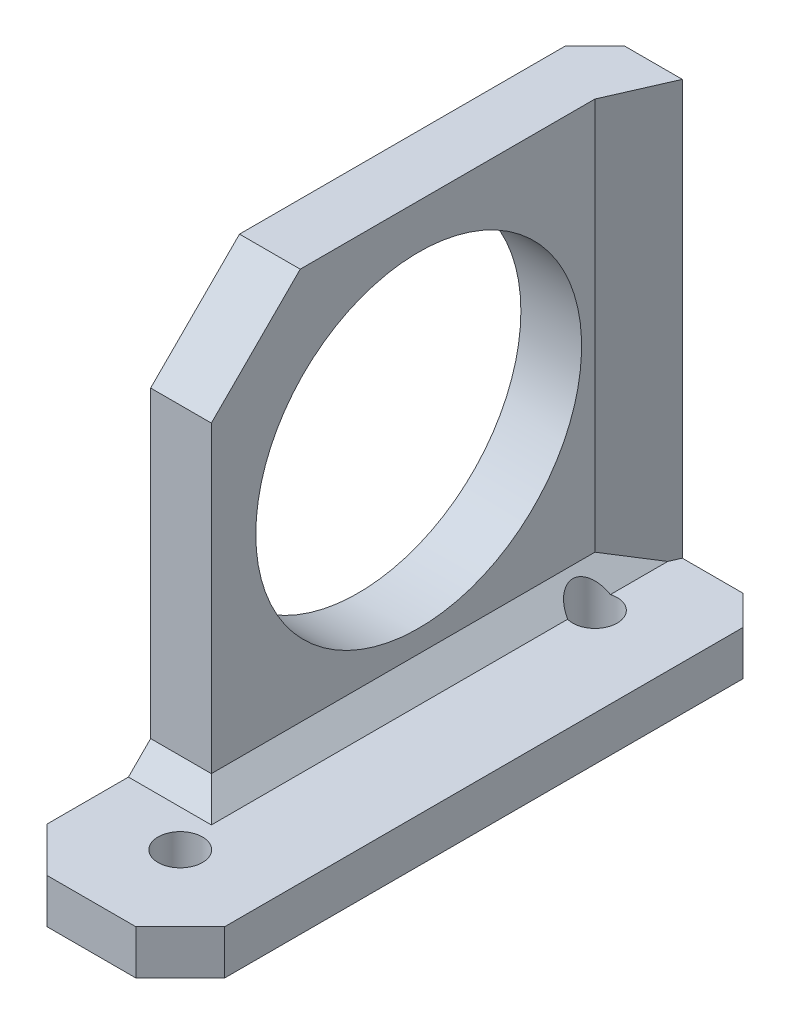
SolidWorks part; units mm, degrees
ref_plane "Front Plane" through (0, 0, 0) normal (0, 0, 1) x (1, 0, 0)
ref_plane "Top Plane" through (0, 0, 0) normal (0, 1, 0) x (1, 0, 0)
ref_plane "Right Plane" through (0, 0, 0) normal (1, 0, 0) x (0, 0, -1)
sketch "Sketch1" plane through (0, 0, 0) normal (0, 1, 0) x (1, 0, 0)
  line L1 (-6, 20) -> (6, 20)
  line L2 (-6, 20) -> (-6, -17)
  line L3 (-3, -20) -> (3, -20)
  line L4 (6, 20) -> (6, -17)
  line L5 (-6, 20) -> (6, -20) construction
  line L6 (-6, -20) -> (6, 20) construction
  line L8 (3, -20) -> (6, -17)
  line L9 (-6, -17) -> (-3, -20)
  circle A0 centre (0, 14) radius 1.5
  circle A1 centre (0, -14) radius 1.5
  point P0 (0, 0)
  dimension "D3" = 3
  dimension "D1" = 40
  dimension "D2" = 12
  dimension "D4" = 14
  dimension "D5" = 14
extrude "Boss-Extrude1" add sketch "Sketch1" along normal blind 3
sketch "Sketch2" plane through (0, 3, 0) normal (0, 1, 0) x (1, 0, 0)
  line L1 (6, -17) -> (6, 20) construction
  line L6 (6, -10) -> (6, 20)
  line L7 (6, 20) -> (0.1, 20)
  line L11 (1.9, -10) -> (1.9, 15.9)
  line L14 (6, 20) -> (-6, 20) construction
  line L16 (6, -10) -> (1.9, -10)
  line L17 (0.1, 20) -> (1.9, 15.9)
  line L18 (1.9, 15.9) -> (0.1, 15.9) construction
  dimension "D2" = 30
  dimension "D3" = 5.9
  dimension "3" = 4.1
extrude "Boss-Extrude2" add sketch "Sketch2" along normal blind 28 contours L16 L11 L17 L7 L6
chamfer "Chamfer1" distance 2 1 edges at (6, 15.5, -20)
sketch "Sketch4" plane through (6, 0, 0) normal (1, 0, 0) x (0, 0, -1)
  line L0 (-10, 31) -> (18, 31) construction
  line L1 (-17, 3) -> (-10, 3) construction
  circle A0 centre (4, 17) radius 11
  point P4 (4, 31)
  dimension "D1" = 22
  dimension "D2" = 14
extrude "Cut-Extrude1" cut sketch "Sketch4" against normal blind 11
chamfer "Chamfer2" distance 6 1 edges at (3.95, 31, 10)
mirror "Mirror3" about plane through (0, 0, 0) normal (1, 0, 0) of "Boss-Extrude2", "Chamfer2", "Cut-Extrude1"
chamfer "Chamfer3" distance 2 1 edges at (-6, 15.5, -20)
sketch "Sketch5" plane through (0, 0, 0) normal (1, 0, 0) x (0, 0, -1)
  line L1 (-10, 3) -> (20, 3)
  line L2 (-10, 3) -> (-10, 31)
  line L3 (-10, 31) -> (20, 31)
  line L4 (20, 3) -> (20, 31)
extrude "Cut-Extrude2" cut sketch "Sketch5" along normal blind 11
chamfer "Chamfer4" distance 1.5 2 edges at (-3.95, 3, 10) (-1.9, 3, -2.95)
